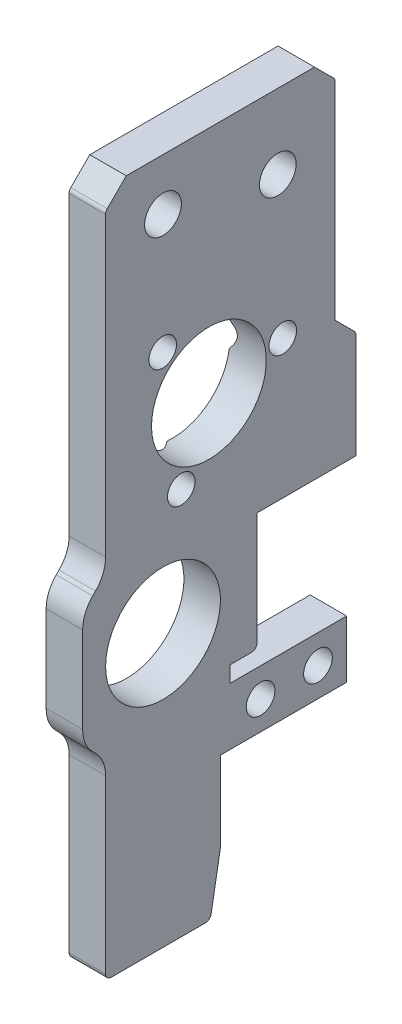
SolidWorks part; units mm, degrees
ref_plane "Front Plane" through (0, 0, 0) normal (0, 0, 1) x (1, 0, 0)
ref_plane "Top Plane" through (0, 0, 0) normal (0, 1, 0) x (1, 0, 0)
ref_plane "Right Plane" through (0, 0, 0) normal (1, 0, 0) x (0, 0, -1)
sketch "Sketch1" plane through (0, 0, 0) normal (1, 0, 0) x (0, 0, -1)
  line L0 (0, 0) -> (0, 16.7)
  line L1 (0, 16.7) -> (-2, 18.7)
  line L2 (-2, 18.7) -> (-2, 28.7)
  line L3 (-2, 28.7) -> (0, 30.7)
  line L4 (0, 30.7) -> (0, 59.81)
  line L5 (0, 59.81) -> (20, 59.81)
  line L7 (21.8, 28.68) -> (13.2, 28.68)
  line L8 (10.85, 18.4) -> (10.85, 17)
  line L9 (10.85, 17) -> (21, 17)
  line L10 (21, 17) -> (21, 12)
  line L11 (21, 12) -> (10, 12)
  line L12 (10, 12) -> (10, 0)
  line L13 (10, 0) -> (0, 0)
  line L14 (-8.9356, -4) -> (60.4069, -4) construction
  line L15 (5, 28.7) -> (-2, 28.7) construction
  line L16 (5, 18.7) -> (-2, 18.7) construction
  line L17 (0, 16.7) -> (0, 30.7) construction
  line L18 (10.85, 18.4) -> (13.2, 18.4)
  line L19 (13.2, 18.4) -> (13.2, 28.68)
  line L23 (20, 59.81) -> (20, 39.81)
  line L26 (20, 39.81) -> (21.8, 39.81)
  line L27 (21.8, 39.81) -> (21.8, 28.68)
  circle A0 centre (5, 23.7) radius 5
  circle A1 centre (5, 55.31) radius 1.6
  circle A2 centre (15, 53.31) radius 1.6
  circle A3 centre (18.5, 14.5) radius 1.25
  circle A4 centre (13.5, 14.5) radius 1.25
  point P12 (5, 0)
  dimension "D11" = 10
  dimension "D13" = 3.2
  dimension "D17" = 5
  dimension "D21" = 2.5
  dimension "D2" = 59.81
  dimension "D3" = 31.13
  dimension "D4" = 5
  dimension "D5" = 11.68
  dimension "D6" = 10.15
  dimension "D7" = 10
  dimension "D8" = 4
  dimension "D9" = 2
  dimension "D10" = 2
  dimension "D12" = 36.11
  dimension "D14" = 6.5
  dimension "D15" = 4.5
  dimension "D16" = 5
  dimension "D18" = 5
  dimension "D19" = 2.5
  dimension "D20" = 2.5
  dimension "D22" = 1.4
  dimension "D23" = 2.35
  dimension "D24" = 20
  dimension "D25" = 11
  dimension "D26" = 1.8
  dimension "D27" = 20
extrude "Boss-Extrude1" add sketch "Sketch1" along normal blind 3.18
chamfer "Chamfer1" distance 5 angle 10 1 edges at (1.59, 0, -10) first distance on face at (1.59, 6, -10)
fillet "Fillet1" [suppressed] radius 1
sketch "Sketch3" plane through (0, 0, 0) normal (-1, 0, 0) x (0, 0, 1)
  line L1 (-15.4326, 40.7448) -> (-4.9749, 44.9147) construction
  line L2 (-4.9749, 44.9147) -> (-6.5925, 33.7732) construction
  line L3 (-6.5925, 33.7732) -> (-15.4326, 40.7448) construction
  line L4 (0, 59.81) -> (0, 30.7) construction
  circle A0 centre (-9, 39.8109) radius 5
  circle A2 centre (-9, 39.8109) radius 6.5 construction
  circle A3 centre (-4.9749, 44.9147) radius 1.2 construction
  circle A4 centre (-6.5925, 33.7732) radius 1.2 construction
  circle A5 centre (-15.4326, 40.7448) radius 1.2 construction
  circle A6 centre (-5, 23.7) radius 5 construction
  dimension "D1" = 10
  dimension "D3" = 16.6
  dimension "D4" = 13
  dimension "D5" = 2.4
  dimension "D2" = 9
hole_wizard "CSK for M2 Flat Head Machine Screw1" positions "Sketch6" profile "Sketch7" countersink size "M2" standard "ANSI Metric"
sketch "Sketch6" plane through (0, 0, 0) normal (-1, 0, 0) x (0, 0, 1)
  point P0 (-4.9749, 44.9147)
  point P3 (-15.4326, 40.7448)
  point P6 (-6.5925, 33.7732)
sketch "Sketch7" plane through (0, 44.9147, -4.9749) normal (0, 1, 0) x (0, 0, 1)
  line L0 (0, 0) -> (0, 4.23)
  line L1 (0, 4.23) -> (1.2, 3.509)
  line L2 (1.2, 3.509) -> (1.2, 1)
  line L3 (1.2, 1) -> (2.2, 0)
  line L5 (2.2, 0) -> (0, 0)
  line L6 (-1.2, 1) -> (-2.2, 0) construction
  line L10 (0, 4.23) -> (-1.2, 3.509) construction
  line L11 (0, -6.35) -> (0, 107.95) construction
  dimension "Hole Dia." = 2.4
  dimension "Hole Depth" = 4.23
  dimension "Near C'Sink Dia." = 4.4
  dimension "Near C'Sink Angle" = 90
  dimension "Drill Angle" = 118
extrude "Cut-Extrude4" cut sketch "Sketch3" against normal through all
sketch "Sketch8" plane through (3.18, 0, 0) normal (1, 0, 0) x (0, 0, -1)
  line L0 (0, 59.81) -> (0, 30.7) construction
  line L1 (9, 39.8109) -> (0, 39.8109) construction
  line L2 (0, 42.8109) -> (2.1261, 42.8109)
  line L3 (2.1261, 36.8109) -> (0, 36.8109)
  line L4 (0, 36.8109) -> (0, 42.8109)
  arc A0 (2.1261, 36.8109) -> (2.1261, 42.8109) centre (9, 39.8109) ccw
  circle A1 centre (5, 23.7) radius 5 construction
  point P11 (0, 39.8109)
  dimension "D1" = 16.6
  dimension "D2" = 15
  dimension "D3" = 9
  dimension "D4" = 6
extrude "Cut-Extrude5" [suppressed] cut sketch "Sketch8" against normal through all
fillet "Fillet2" radius 3 4 edges at (1.59, 16.7, 0) (1.59, 18.7, 2) (1.59, 28.7, 2) (1.59, 30.7, 0)
fillet "Chamfer2" radius 1.8 3 edges at (1.59, 59.81, -20) (1.59, 59.81, 0) (1.59, 39.81, -21.8) profile chamfer
fillet "Fillet4" radius 0.5 6 edges at (1.59, 58.01, 0) (1.59, 0, 0) (1.59, 58.01, -20) (1.59, 18.4, -13.2) (1.59, 0, -9.1184) (1.59, 38.01, -21.8)
